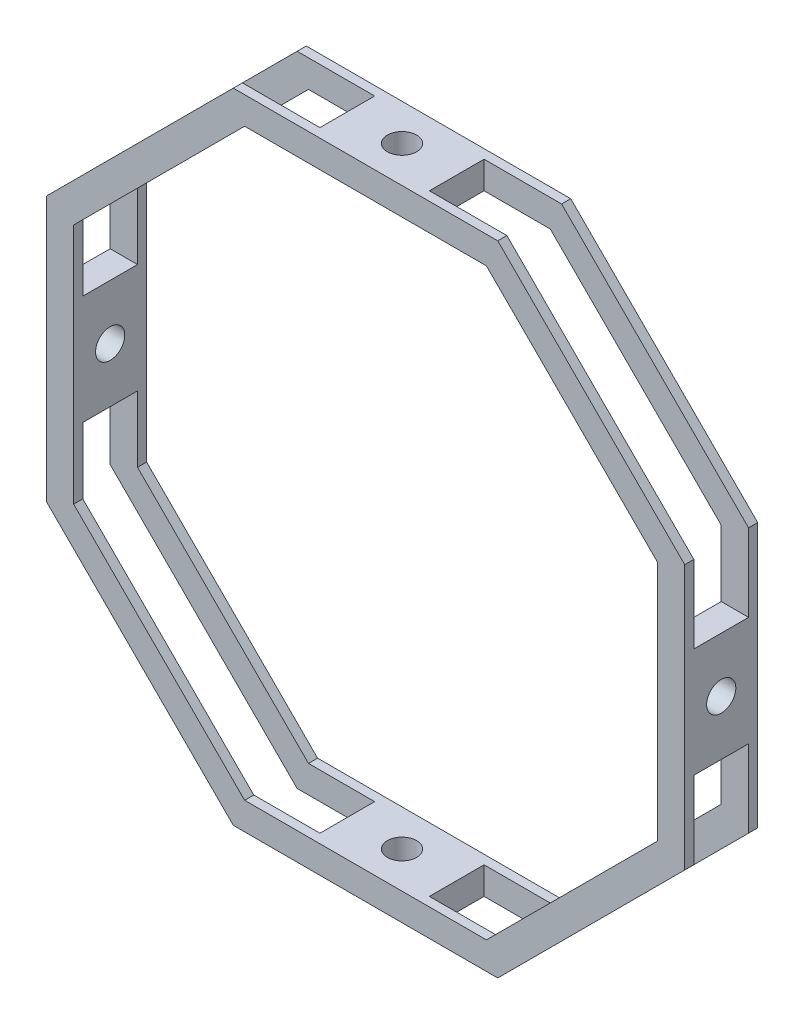
SolidWorks part; units mm, degrees
ref_plane "Plano frontal" through (0, 0, 0) normal (0, 0, 1) x (1, 0, 0)
ref_plane "Plano superior" through (0, 0, 0) normal (0, 1, 0) x (1, 0, 0)
ref_plane "Plano direito" through (0, 0, 0) normal (1, 0, 0) x (0, 0, -1)
sketch "Esboço1" plane through (0, 0, 0) normal (0, 0, 1) x (1, 0, 0)
  line L9 (175, 72.4874) -> (72.4874, 175)
  line L10 (72.4874, 175) -> (-72.4874, 175)
  line L11 (-72.4874, 175) -> (-175, 72.4874)
  line L12 (-175, 72.4874) -> (-175, -72.4874)
  line L13 (-175, -72.4874) -> (-72.4874, -175)
  line L14 (-72.4874, -175) -> (72.4874, -175)
  line L15 (72.4874, -175) -> (175, -72.4874)
  line L16 (175, -72.4874) -> (175, 72.4874)
  line L17 (160, 66.2742) -> (66.2742, 160)
  line L18 (66.2742, 160) -> (-66.2742, 160)
  line L19 (-66.2742, 160) -> (-160, 66.2742)
  line L20 (-160, 66.2742) -> (-160, -66.2742)
  line L21 (-160, -66.2742) -> (-66.2742, -160)
  line L22 (-66.2742, -160) -> (66.2742, -160)
  line L23 (66.2742, -160) -> (160, -66.2742)
  line L24 (160, -66.2742) -> (160, 66.2742)
  circle A0 centre (0, 0) radius 175 construction
  circle A1 centre (0, 0) radius 160 construction
extrude "Ressalto-extrusão1" add sketch "Esboço1" along normal blind 40
sketch "Esboço2" plane through (175, 0, 0) normal (1, 0, 0) x (0, 0, -1)
  line L0 (-40, 72.4874) -> (0, 72.4874) construction
  line L1 (-40, -72.4874) -> (-40, 72.4874) construction
  line L3 (0, 0) -> (0, 29.9874)
  line L4 (0, 29.9874) -> (-40, 29.9874)
  line L5 (-40, 0) -> (-40, 29.9874)
  line L6 (0, 29.9874) -> (-5, 29.9874)
  line L8 (0, 0) -> (0, -30)
  line L9 (0, -30) -> (-40, -30)
  line L10 (-40, 0) -> (-40, -30)
  line L11 (0, 29.9874) -> (0, 72.4874)
  line L12 (0, 72.4874) -> (-5, 72.4874)
  line L13 (-5, 29.9874) -> (-5, 72.4874)
  line L14 (-40, -72.4874) -> (0, -72.4874) construction
  line L15 (-40, 29.9874) -> (-35, 29.9874)
  line L16 (-40, 29.9874) -> (-40, 72.4874)
  line L17 (-40, 72.4874) -> (-35, 72.4874)
  line L18 (-35, 29.9874) -> (-35, 72.4874)
  line L19 (-40, -30) -> (-35, -30)
  line L20 (-40, -30) -> (-40, -72.4874)
  line L21 (-40, -72.4874) -> (-35, -72.4874)
  line L22 (-35, -30) -> (-35, -72.4874)
  line L24 (0, -30) -> (-5, -30)
  line L25 (0, -30) -> (0, -72.4874)
  line L26 (0, -72.4874) -> (-5, -72.4874)
  line L27 (-5, -30) -> (-5, -72.4874)
  line M5 (0, 72.4874) -> (-40, 72.4874)
  line M7 (-40, -72.4874) -> (0, -72.4874)
extrude "Corte-extrusão2" cut sketch "Esboço2" against normal through all both and the other way through all contours L18 L4 L13 M5 region at (175, 51.2374, 20)
sketch "Esboço4" plane through (175, 0, 0) normal (1, 0, 0) x (0, 0, -1)
  circle A0 centre (-20, 0) radius 8
  point P2 (-19.5328, 0)
extrude "Corte-extrusão3" cut sketch "Esboço4" against normal through all both and the other way through all
extrude "Corte-extrusão4" cut sketch "Esboço2<4>" against normal through all both and the other way through all contours L27 L9 L22 M7 region at (175, -51.2437, 20)
sketch "Esboço2<4>" plane through (175, 0, 0) normal (1, 0, 0) x (0, 0, -1) same geometry as "Esboço2"
sketch "Esboço15" plane through (-123.7437, 123.7437, 0) normal (-0.7071, 0.7071, 0) x (0, 0, 1)
  line L0 (40, 72.4874) -> (0, 72.4874) construction
  line L1 (5, -72.4874) -> (35, -72.4874)
  line L2 (5, -72.4874) -> (5, 72.4874)
  line L3 (5, 72.4874) -> (35, 72.4874)
  line L4 (35, -72.4874) -> (35, 72.4874)
extrude "Corte-extrusão5" cut sketch "Esboço15" against normal through all both and the other way through all
sketch "Esboço16" plane through (123.7437, 123.7437, 0) normal (0.7071, 0.7071, 0) x (0, 0, -1)
  line L0 (-40, 72.4874) -> (0, 72.4874) construction
  line L1 (-35, -72.4874) -> (-5, -72.4874)
  line L2 (-35, -72.4874) -> (-35, 72.4874)
  line L3 (-35, 72.4874) -> (-5, 72.4874)
  line L4 (-5, -72.4874) -> (-5, 72.4874)
extrude "Corte-extrusão6" cut sketch "Esboço16" against normal through all both and the other way through all
sketch "Esboço18" plane through (0, -175, 0) normal (0, -1, 0) x (1, 0, 0)
  line L1 (-72.4874, 35) -> (72.4874, 35)
  line L2 (-72.4874, 35) -> (-72.4874, 5)
  line L3 (-72.4874, 5) -> (72.4874, 5)
  line L4 (72.4874, 35) -> (72.4874, 5)
ref_plane "Plano2" through (160, -30, 5) normal (1, 0, 0) x (0, 0, -1)
sketch "Esboço21" plane through (0, 175, 0) normal (0, 1, 0) x (1, 0, 0)
  line L0 (-72.4874, -5) -> (72.4874, -5) construction
  line L1 (0, -5) -> (30, -5)
  line L2 (0, -5) -> (0, -35)
  line L3 (0, -35) -> (30, -35)
  line L4 (30, -5) -> (30, -35)
  line L5 (-72.4874, -35) -> (72.4874, -35) construction
  line L7 (0, -5) -> (-30, -5)
  line L8 (0, -5) -> (0, -35)
  line L9 (0, -35) -> (-30, -35)
  line L10 (-30, -5) -> (-30, -35)
sketch "Esboço22" plane through (0, 175, 0) normal (0, 1, 0) x (1, 0, 0)
  line L1 (-30, -5) -> (-72.4874, -5)
  line L2 (-30, -5) -> (-30, -35)
  line L3 (-30, -35) -> (-72.4874, -35)
  line L4 (-72.4874, -5) -> (-72.4874, -35)
  line L5 (30, -5) -> (72.4874, -5)
  line L6 (30, -5) -> (30, -35)
  line L7 (30, -35) -> (72.4874, -35)
  line L8 (72.4874, -5) -> (72.4874, -35)
extrude "Corte-extrusão8" cut sketch "Esboço22" against normal through all both and the other way through all
sketch "Esboço23" plane through (0, 175, 0) normal (0, 1, 0) x (1, 0, 0)
  line L0 (0, -5) -> (0, -35) construction
  circle A0 centre (0, -20) radius 8
extrude "Corte-extrusão9" cut sketch "Esboço23" against normal through all both and the other way through all
